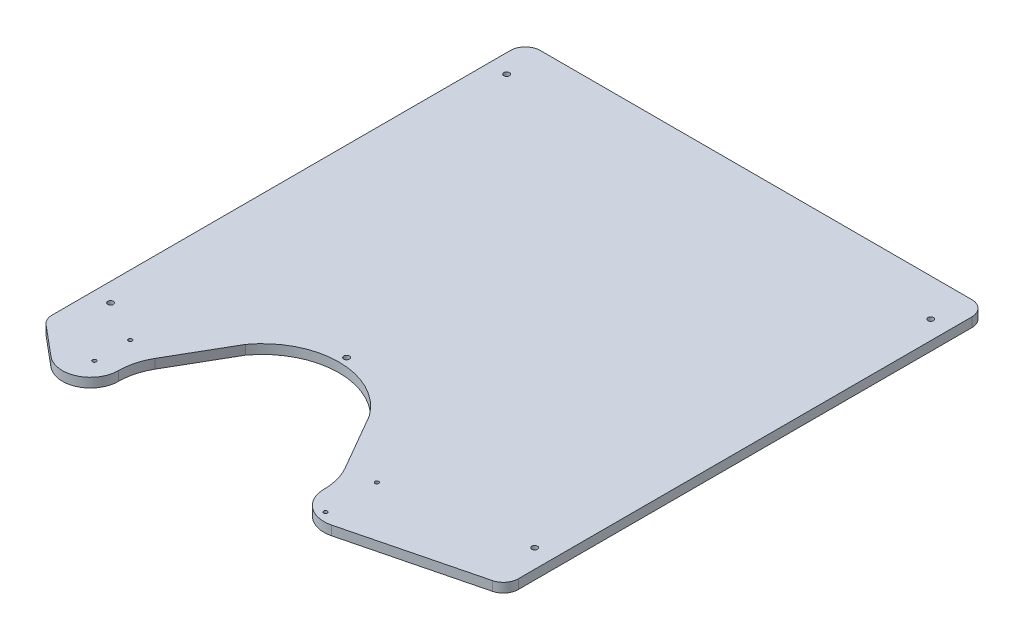
SolidWorks part; units mm, degrees
material "ABS PC"
ref_plane "Plan de face" through (0, 0, 0) normal (0, 0, 1) x (1, 0, 0)
ref_plane "Plan de dessus" through (0, 0, 0) normal (0, 1, 0) x (1, 0, 0)
ref_plane "Plan de droite" through (0, 0, 0) normal (1, 0, 0) x (0, 0, -1)
sketch "Esquisse1" plane through (0, 0, 0) normal (0, 1, 0) x (1, 0, 0)
  line L0 (-60.6815, -188.3301) -> (-75.8539, -214.6094) construction
  line L1 (-115.5, 31.2) -> (115.5, 31.2)
  line L2 (-123.5, 23.2) -> (-123.5, -222.0619)
  line L3 (-60.6815, -188.3301) -> (-75.8539, -214.6094)
  line L4 (123.5, 23.2) -> (123.5, -219.5635)
  line L5 (25.8539, -214.6094) -> (10.6815, -188.3301) construction
  line L6 (25.8539, -214.6094) -> (10.6815, -188.3301)
  line L7 (8.1815, -184) -> (10.6815, -188.3301)
  line L8 (-58.1815, -184) -> (-60.6815, -188.3301)
  line L9 (-120.6327, -228.1983) -> (-104.6238, -241.5886)
  line L10 (117.4519, -227.3217) -> (48.6599, -244.6295)
  line L12 (-108.5, -220.8) -> (-118.5, -220.8) construction
  line L15 (-118.5, -220.8) -> (-118.5, 31.2) construction
  line L16 (118.5, -220.8) -> (118.5, 31.2) construction
  line L18 (108.5, 31.2) -> (-108.5, 31.2) construction
  arc A0 (8.1815, -184) -> (-58.1815, -184) centre (-25, -208.0829) ccw construction
  arc A1 (8.1815, -184) -> (-58.1815, -184) centre (-25, -208.0829) ccw
  arc A4 (30, -230.0829) -> (45, -245.0829) centre (45, -230.0829) ccw construction
  arc A5 (30, -230.0829) -> (25.8539, -214.6094) centre (-0.9469, -230.0829) ccw construction
  arc A6 (30, -230.0829) -> (25.8539, -214.6094) centre (-0.9469, -230.0829) ccw
  arc A7 (-95, -245.0829) -> (-80, -230.0829) centre (-95, -230.0829) ccw construction
  circle A8 centre (41, -212.75) radius 1
  circle A9 centre (41, -240.25) radius 1
  arc A10 (-115.5, 31.2) -> (-123.5, 23.2) centre (-115.5, 23.2) ccw
  arc A11 (115.5, 31.2) -> (123.5, 23.2) centre (115.5, 23.2) cw
  arc A12 (117.4519, -227.3217) -> (123.5, -219.5635) centre (115.5, -219.5635) ccw
  arc A13 (-123.5, -222.0619) -> (-120.6327, -228.1983) centre (-115.5, -222.0619) ccw
  arc A14 (-87.0138, -242.7801) -> (-80, -230.0829) centre (-95, -230.0829) ccw
  arc A15 (-75.8539, -214.6094) -> (-80, -230.0829) centre (-49.0531, -230.0829) ccw construction
  arc A16 (-75.8539, -214.6094) -> (-80, -230.0829) centre (-49.0531, -230.0829) ccw
  arc A17 (30, -230.0829) -> (42.3384, -244.8448) centre (45, -230.0829) ccw
  arc A18 (42.3384, -244.8448) -> (48.6599, -244.6295) centre (45, -230.0829) ccw
  arc A19 (-87.0138, -242.7801) -> (-104.6238, -241.5886) centre (-95, -230.0829) cw
  circle A20 centre (-91, -212.75) radius 1
  circle A21 centre (-91, -232) radius 1
  point P31 (-123.5, -225.8)
  point P44 (123.5, -225.8)
  dimension "D2" = 2
  dimension "D6" = 8
  dimension "D3" = 5
  dimension "D4" = 5
  dimension "D5" = 5
extrude "Boss.-Extru.1" add sketch "Esquisse1" against normal blind 5
sketch "Esquisse2" plane through (0, 0, 0) normal (0, 1, 0) x (1, 0, 0)
  circle A0 centre (-113.5, 11.2) radius 1.5
  circle A1 centre (-25, -163) radius 1.5
  circle A2 centre (113.5, 11.2) radius 1.5
  circle A3 centre (113.5, -200.8) radius 1.5
  circle A4 centre (-113.5, -200.8) radius 1.5
  dimension "D1" = 3
extrude "Enlèv. mat.-Extru.1" cut sketch "Esquisse2" against normal through all
